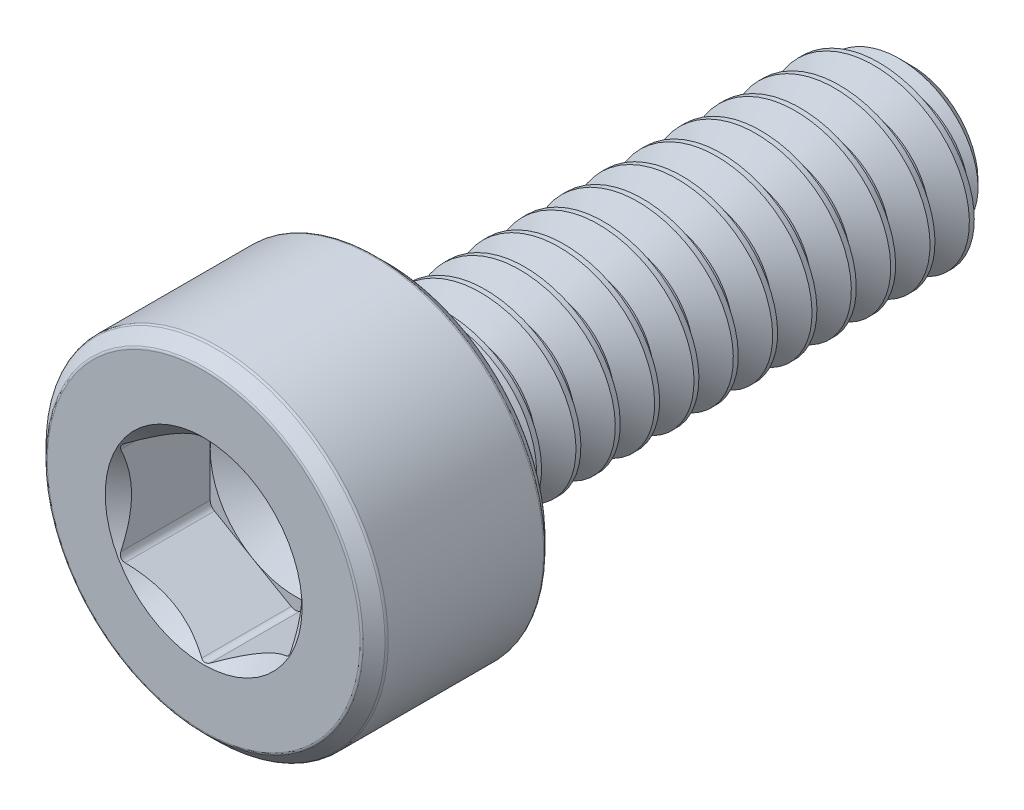
SolidWorks part; units mm, degrees
ref_plane "Front Plane" through (0, 0, 0) normal (0, 0, 1) x (1, 0, 0)
ref_plane "Top Plane" through (0, 0, 0) normal (0, 1, 0) x (1, 0, 0)
ref_plane "Right Plane" through (0, 0, 0) normal (1, 0, 0) x (0, 0, -1)
sketch "Sketch1" plane through (0, 0, 0) normal (1, 0, 0) x (0, 0, -1)
  line L0 (-2.7, 0) -> (2.7, 0) construction
  line L1 (-2.7, 0) -> (-2.7, 1.3)
  line L2 (-2.7, 1.3) -> (-1.3, 1.3)
  line L3 (-1.3, 1.3) -> (-1.3, 0.7)
  line L4 (-1.3, 0.7) -> (2.5051, 0.7)
  line L5 (2.6812, 0.7325) -> (2.8312, 0.4727) construction
  line L6 (2.8312, 0.4727) -> (2.9813, 0.7325) construction
  line L7 (2.9813, 0.7325) -> (2.6812, 0.7325) construction
  line L8 (2.5051, 0.7) -> (2.7, 0.5051)
  line L9 (2.7, 0.5051) -> (2.7, 0)
  line L10 (2.7, 0.7) -> (2.9625, 0.7) construction
  line L11 (2.8312, 0.7325) -> (2.8313, 0.7) construction
  line L12 (2.8313, 0.7) -> (2.8312, 0.5051) construction
  line L13 (2.8312, 0.5051) -> (2.8312, 0.4727) construction
  line L14 (2.8125, 0.5051) -> (2.85, 0.5051)
  line L15 (2.6906, 0.7162) -> (2.9719, 0.7162)
  line L16 (2.85, 0.5051) -> (2.9719, 0.7162)
  line L17 (2.8125, 0.5051) -> (2.6906, 0.7162)
  line L18 (-2.7, 0.65) -> (-2, 0.65)
  line L19 (-2, 0.65) -> (-2, 0)
  line L20 (1.65, 0.7) -> (1.65, -0.7) construction
  point P20 (2.8312, 0.7162)
  point P22 (1.65, -0.7)
  point P28 (1.65, 0)
  point P29 (2.5051, -0.7)
  dimension "Head Diameter" = 2.6
  dimension "Length" = 4
  dimension "Head Height" = 1.4
  dimension "Thread Size" = 1.4
  dimension "D1" = 45
  dimension "Thread Pitch" = 0.3
  dimension "D3" = 0.0375
  dimension "Drive Size" = 1.3
  dimension "D4" = 1.05
  dimension "D5" = 0.7
sketch "Sketch3" plane through (0, 0, 0) normal (1, 0, 0) x (0, 0, -1)
  line L0 (-2.7, 1.1924) -> (-2.7, 0.65)
  line L1 (-2.7, 0.65) -> (-2, 0.65)
  line L2 (-2, 0.65) -> (-2, 0)
  line L3 (-2, 0) -> (2.7, 0)
  line L4 (2.7, 0) -> (2.7, 0.5051)
  line L5 (2.7, 0.5051) -> (2.5051, 0.7)
  line L6 (2.5051, 0.7) -> (-1.3, 0.7)
  line L7 (-1.3, 0.7) -> (-1.3, 1.1924)
  line L8 (-1.4076, 1.3) -> (-2.5924, 1.3)
  line L9 (-2.6929, 1.2096) -> (-2.6096, 1.2929)
  line L11 (-2.7, 1.3) -> (-1.3, 1.3) construction
  line L12 (-1.3904, 1.2929) -> (-1.3071, 1.2096)
  arc A5 (-1.3071, 1.2096) -> (-1.3, 1.1924) centre (-1.3244, 1.1924) cw
  arc A6 (-1.4076, 1.3) -> (-1.3904, 1.2929) centre (-1.4076, 1.2756) cw
  arc A7 (-2.5924, 1.3) -> (-2.6096, 1.2929) centre (-2.5924, 1.2756) ccw
  arc A8 (-2.7, 1.1924) -> (-2.6929, 1.2096) centre (-2.6756, 1.1924) cw
  point P17 (-2, 1.3)
  point P29 (-2.7, 1.2025)
  dimension "D3" = 0.0244
  dimension "D1" = 45
  dimension "D2" = 0.0975
revolve "Revolve1" add sketch "Sketch3" angle 360 about L0
sketch "Sketch4" plane through (0, 0, 2.7) normal (0, 0, 1) x (1, 0, 0)
  line L1 (0, 0.7506) -> (-0.65, 0.3753)
  line L2 (-0.65, 0.3753) -> (-0.65, -0.3753)
  line L3 (-0.65, -0.3753) -> (0, -0.7506)
  line L4 (0, -0.7506) -> (0.65, -0.3753)
  line L5 (0.65, -0.3753) -> (0.65, 0.3753)
  line L6 (0.65, 0.3753) -> (0, 0.7506)
  circle A0 centre (0, 0) radius 0.65 construction
extrude "Cut-Extrude1" cut sketch "Sketch4" against normal up to vertex (0.7 mm away) up to point (0, 0.65, 2)
sketch "Sketch5" plane through (0, 0, 2.7) normal (0, 0, 1) x (1, 0, 0)
  circle A0 centre (0, 0) radius 0.7506
extrude "Cut-Extrude2" cut sketch "Sketch5" against normal up to next (0.7 mm away) draft 45
sketch "Sketch10" plane through (0, 0, 2) normal (0, 0, 1) x (1, 0, 0)
  line L0 (0.65, 0.3753) -> (0.65, -0.3753) construction
  circle A0 centre (0, 0) radius 0.65
extrude "Cut-Extrude3" cut sketch "Sketch10" against normal through all draft 60
fillet "Fillet1" radius 0.065 6 edges at (-0.65, 0.3753, 2.35) (0, 0.7506, 2.35) (0.65, 0.3753, 2.35) (0.65, -0.3753, 2.35) (0, -0.7506, 2.35) (-0.65, -0.3753, 2.35)
sketch "Sketch6" plane through (0, 0, -2.7) normal (0, 0, -1) x (-1, 0, 0)
  circle A0 centre (0, 0) radius 0.7 construction
  circle A1 centre (0, 0) radius 0.7
curve "Helix/Spiral1" pitch 0.3 height 4.3 radius 0.7 centre (0, 0, -2.7) axis (0, 0, 1) start towards (0, 1, 0)
sketch "Sketch7" plane through (0, 0, 0) normal (1, 0, 0) x (0, 0, -1)
  line L0 (2.8125, 0.5051) -> (2.85, 0.5051) construction
  line L1 (2.8125, 0.5051) -> (2.6906, 0.7162) construction
  line L2 (2.6906, 0.7162) -> (2.9719, 0.7162) construction
  line L3 (2.85, 0.5051) -> (2.9719, 0.7162) construction
  line L4 (2.8125, 0.5051) -> (2.85, 0.5051)
  line L5 (2.8125, 0.5051) -> (2.6906, 0.7162)
  line L6 (2.6906, 0.7162) -> (2.9719, 0.7162)
  line L7 (2.85, 0.5051) -> (2.9719, 0.7162)
sweep "Cut-Sweep1" cut profiles "Sketch7" path "Helix/Spiral1" align with end faces yes
sketch "Sketch11" plane through (0, 0, 0) normal (1, 0, 0) x (0, 0, -1)
  line L0 (-1.3, 0.775) -> (-1.225, 0.7) construction
  line L1 (-1.3, 1.3) -> (-1.3, 0.7) construction
  line L2 (-1.3, 0.7) -> (2.5051, 0.7) construction
  line L3 (-1.225, 0.7) -> (-1.15, 0.7)
  line L4 (-1.15, 0.7) -> (-0.45, 0)
  line L5 (-2.7, 0) -> (2.7, 0) construction
  line L6 (-0.45, 0) -> (-1.3, 0)
  line L7 (-1.3, 0) -> (-1.3, 0.775) construction
  line L8 (-1.3, 0.775) -> (-1.6247, 0.775)
  line L9 (-1.6247, 0.775) -> (-1.6247, 0)
  line L10 (-1.6247, 0) -> (-1.3, 0)
  arc A0 (-1.225, 0.7) -> (-1.3, 0.775) centre (-1.225, 0.775) cw
  dimension "D1" = 45
  dimension "D2" = 0.075
  dimension "D3" = 45
  dimension "D4" = 0.15
revolve "Revolve2" add sketch "Sketch11" angle 360 about L6
equation "\"D3@Sketch1\" = \"Thread Pitch@Sketch1\" / 8"
equation "\"D4@Sketch1\" = \"Thread Pitch@Sketch1\" * 3.5"
equation "\"D3@Helix/Spiral1\" = \"Length@Sketch1\" + \"Thread Pitch@Sketch1\""
equation "\"D4@Helix/Spiral1\" = \"Thread Pitch@Sketch1\""
equation "\"D5@Sketch1\"=\"Head Height@Sketch1\"*0.5"
equation "\"D2@Sketch3\"=\"Head Diameter@Sketch1\" *0.0375"
equation "\"D2@Sketch11\"=\"Thread Pitch@Sketch1\" / 4"
equation "\"D4@Sketch11\"=\"Thread Pitch@Sketch1\"/2"
equation "\"D1@Fillet1\"=\"Drive Size@Sketch1\"*0.05"
equation "\"D1@Fillet1\" = \"Drive Size@Sketch1\" * 0.05"
equation "\"D3@Sketch3\"=\"D2@Sketch3\"*0.25"
